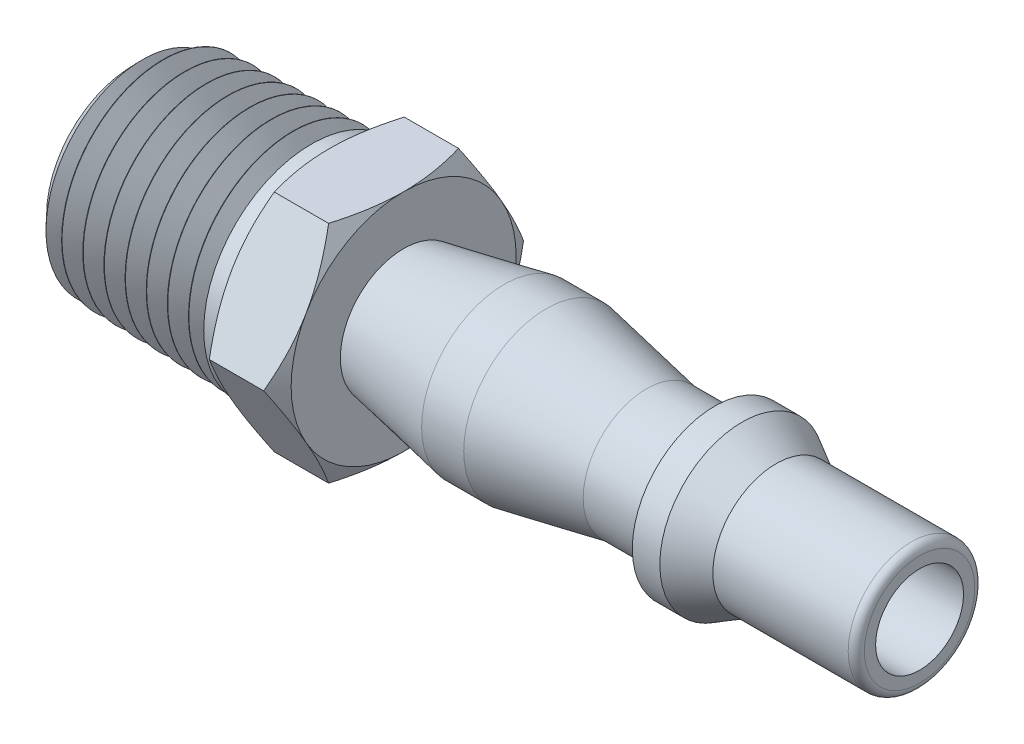
SolidWorks part; units mm, degrees
other "Camera2"
ref_plane "Front" through (0, 0, 0) normal (0, 0, 1) x (1, 0, 0)
ref_plane "Top" through (0, 0, 0) normal (0, 1, 0) x (1, 0, 0)
ref_plane "Right" through (0, 0, 0) normal (1, 0, 0) x (0, 0, -1)
sketch "Sketch1" plane through (0, 0, 0) normal (0, 0, 1) x (1, 0, 0)
  line L0 (0, 0) -> (48.6, 0) construction
  line L1 (0, 6.35) -> (0, 2.715)
  line L2 (0, 2.715) -> (48.6, 2.715)
  line L3 (48.6, 2.715) -> (48.6, 3.91)
  line L4 (48.6, 3.91) -> (39.74, 3.91)
  line L5 (39.74, 3.91) -> (37.64, 5.085)
  line L6 (37.64, 5.085) -> (35.94, 5.085)
  line L7 (35.94, 5.085) -> (35.94, 3.91)
  line L8 (35.94, 3.91) -> (31.73, 3.91)
  line L9 (31.73, 3.91) -> (25.53, 5.09)
  line L10 (25.53, 5.09) -> (22.93, 5.09)
  line L11 (22.93, 5.09) -> (16.73, 3.91)
  line L12 (16.73, 3.91) -> (16.73, 10)
  line L13 (16.73, 10) -> (12.13, 10)
  line L14 (12.13, 10) -> (12.13, 6.65)
  line L15 (12.13, 6.65) -> (11.03, 6.65)
  line L16 (11.03, 6.65) -> (11.03, 6.6003)
  line L17 (11.03, 6.6003) -> (0, 6.35)
  line L18 (24.23, 5.09) -> (24.23, 2.715) construction
  dimension "D1" = 48.6
  dimension "D2" = 5.43
  dimension "D3" = 7.82
  dimension "D4" = 10.17
  dimension "D5" = 8.86
  dimension "D6" = 12.66
  dimension "D7" = 1.7
  dimension "D8" = 7.5
  dimension "D9" = 2.6
  dimension "D10" = 31.87
  dimension "D11" = 10.18
  dimension "D12" = 20
  dimension "D13" = 13.3
  dimension "D14" = 12.7
  dimension "D15" = 1.3
  dimension "D16" = 4.6
  dimension "D17" = 5.7
revolve "Revolve1" add sketch "Sketch1" angle 360 about L0
sketch "Sketch2" plane through (12.13, 0, 0) normal (-1, 0, 0) x (0, 0, 1)
  line L1 (-4.0126, 6.95) -> (-8.0252, 0)
  line L2 (-8.0252, 0) -> (-4.0126, -6.95)
  line L3 (-4.0126, -6.95) -> (4.0126, -6.95)
  line L4 (4.0126, -6.95) -> (8.0252, 0)
  line L5 (8.0252, 0) -> (4.0126, 6.95)
  line L6 (4.0126, 6.95) -> (-4.0126, 6.95)
  circle A0 centre (0, 0) radius 6.95 construction
  circle A1 centre (0, 0) radius 10 construction
  circle A2 centre (0, 0) radius 10
  dimension "D1" = 13.9
extrude "Cut-Extrude1" cut sketch "Sketch2" against normal through all
sketch "Sketch3" plane through (0, 0, 0) normal (0, 1, 0) x (1, 0, 0)
  line L0 (12.13, 6.95) -> (12.7507, 8.0252)
  line L1 (12.13, 4.0126) -> (12.13, 8.0252) construction
  line L2 (16.73, 8.0252) -> (12.13, 8.0252) construction
  line L3 (12.7507, 8.0252) -> (12.13, 8.0252)
  line L4 (12.13, 8.0252) -> (12.13, 6.95)
  line L5 (14.43, 8.0252) -> (14.43, 4.0126) construction
  line L6 (16.73, 4.0126) -> (12.13, 4.0126) construction
  line L7 (16.73, 8.0252) -> (16.73, 6.95)
  line L8 (16.1093, 8.0252) -> (16.73, 8.0252)
  line L9 (16.73, 6.95) -> (16.1093, 8.0252)
  line L10 (0, 0) -> (26.2475, 0) construction
  line L11 (0, 6.35) -> (0, -6.35) construction
  dimension "D1" = 6.95
  dimension "D2" = 30
revolve "Cut-Revolve1" cut sketch "Sketch3" angle 360 about L10
chamfer "Chamfer1" distance 1 angle 45 1 edges at (0, 0, 6.35)
fillet "Fillet1" radius 0.5 1 edges at (48.6, 0, 3.91)
sketch "Sketch4" plane through (0, 0, 0) normal (-1, 0, 0) x (0, 0, 1)
  circle A0 centre (0, 0) radius 6.3727 construction
  circle A1 centre (0, 0) radius 6.3727
curve "Helix/Spiral1"
sketch "Sketch5" plane through (0, 0, 0) normal (0, 1, 0) x (1, 0, 0)
  line L0 (0.6684, -6.3727) -> (-0.6684, -6.3727)
  line L1 (-0.6684, -6.3727) -> (0, -5.2149)
  line L2 (0, -5.2149) -> (0, -6.3727) construction
  line L3 (0.6684, -6.3727) -> (0, -5.2149)
  dimension "D1" = 60
  dimension "D2" = 1.3368
sweep "Cut-Sweep1" cut profiles "Sketch5" path "Helix/Spiral1"
